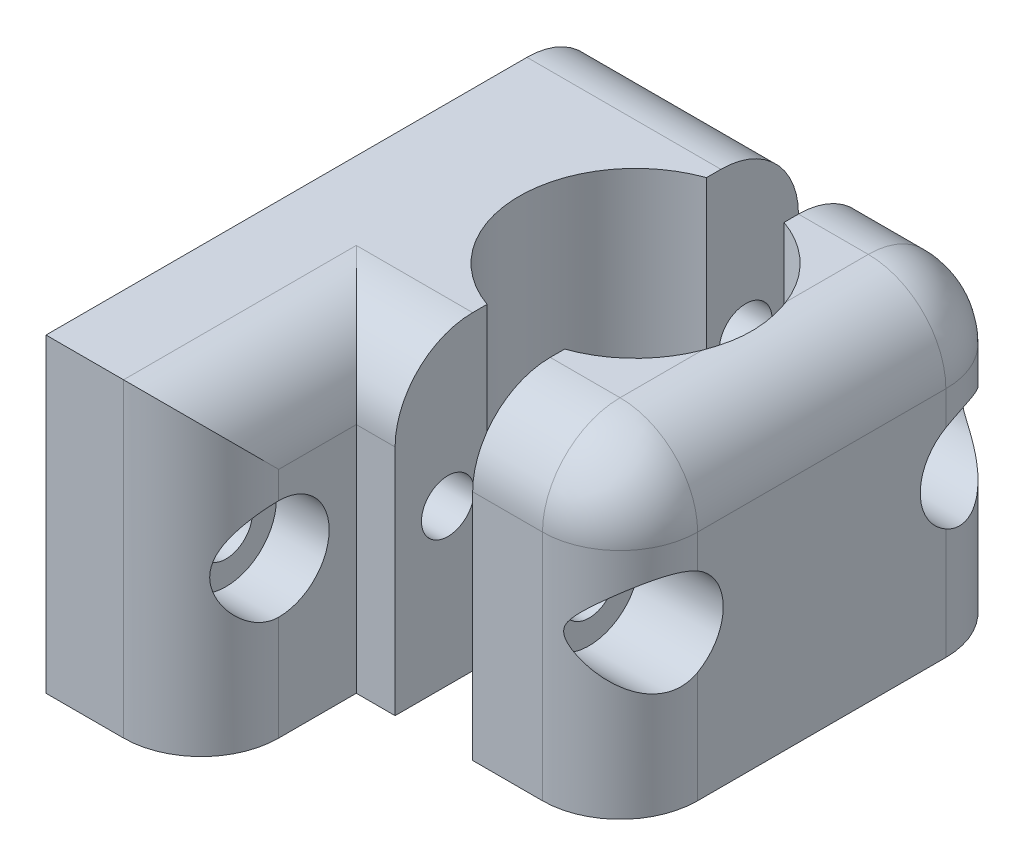
SolidWorks part; units mm, degrees
material "ABS"
ref_plane "Front Plane" through (0, 0, 0) normal (0, 0, 1) x (1, 0, 0)
ref_plane "Top Plane" through (0, 0, 0) normal (0, 1, 0) x (1, 0, 0)
ref_plane "Right Plane" through (0, 0, 0) normal (1, 0, 0) x (0, 0, -1)
sketch "Sketch1" plane through (0, 0, 0) normal (1, 0, 0) x (0, 0, -1)
  line L1 (-13, -10) -> (13, -10)
  line L2 (-13, -10) -> (-13, 10)
  line L3 (-13, 10) -> (13, 10)
  line L4 (13, -10) -> (13, 10)
  line L5 (-13, -10) -> (13, 10) construction
  line L6 (-13, 10) -> (13, -10) construction
  point P0 (0, 0)
  dimension "D1" = 20
  dimension "D2" = 26
extrude "Boss-Extrude1" add sketch "Sketch1" along normal blind 30
sketch "Sketch2" plane through (0, 10, 0) normal (0, 1, 0) x (1, 0, 0)
  line L0 (0, 13) -> (0, -13) construction
  circle A0 centre (15, 0) radius 7.5
  dimension "D1" = 15
  dimension "D2" = 15
extrude "Cut-Extrude1" cut sketch "Sketch2" against normal through all
ref_plane "Plane1" through (0, 0, 0) normal (0, 0, -1) x (-1, 0, 0)
sketch "Sketch4" plane through (0, 0, 13) normal (0, 0, 1) x (1, 0, 0)
  line L0 (30, -10) -> (0, -10) construction
  line L1 (0, 10) -> (10, 10)
  line L2 (0, 10) -> (0, -10)
  line L3 (0, -10) -> (10, -10)
  line L4 (10, 10) -> (10, -10)
  dimension "D1" = 10
extrude "Boss-Extrude2" add sketch "Sketch4" along normal blind 10
hole_wizard "CBORE for M3 Hex Socket Head Cap Screw1" positions "Sketch5" profile "Sketch6" counterbore size "M3" standard "ISO" end condition through all
sketch "Sketch5" plane through (10, 0, 0) normal (1, 0, 0) x (0, 0, -1)
  line L0 (-23, -10) -> (-23, 10) construction
  point P0 (-18, 0)
  dimension "D1" = 5
sketch "Sketch6" plane through (10, 0, 18) normal (0, 1, 0) x (0, 0, -1)
  line L0 (0, 0) -> (0, 10)
  line L1 (0, 10) -> (1.7, 10)
  line L3 (1.7, 10) -> (1.7, 3.4)
  line L4 (1.7, 3.4) -> (3.25, 3.4)
  line L5 (3.25, 3.4) -> (3.25, 0)
  line L7 (3.25, 0) -> (0, 0)
  line L11 (0, -6.35) -> (0, 107.95) construction
  dimension "Thru Hole Dia." = 3.4
  dimension "Thru Hole Depth" = 10
  dimension "C'Bore Dia." = 6.5
  dimension "C'Bore Depth" = 3.4
sketch "Sketch13" plane through (0, 10, 0) normal (0, 1, 0) x (1, 0, 0)
  line L0 (30, 13) -> (0, 13) construction
  line L1 (30, -13) -> (27, -13)
  line L2 (30, -13) -> (30, 13)
  line L3 (30, 13) -> (27, 13)
  line L4 (27, -13) -> (27, 13)
  dimension "D1" = 3
extrude "Cut-Extrude4" cut sketch "Sketch13" against normal through all
hole_wizard "CBORE for M3 Hex Socket Head Cap Screw3" positions "Sketch14" profile "Sketch15" counterbore size "M3" standard "ISO" end condition through all
sketch "Sketch14" plane through (27, 0, 0) normal (1, 0, 0) x (0, 0, -1)
  line L0 (-13, -10) -> (-13, 10) construction
  point P0 (-9.6, 0)
  dimension "D1" = 3.4
sketch "Sketch15" plane through (27, 0, 9.6) normal (0, 1, 0) x (0, 0, -1)
  line L0 (0, 0) -> (0, 27)
  line L1 (0, 27) -> (1.7, 27)
  line L3 (1.7, 27) -> (1.7, 5.4)
  line L4 (1.7, 5.4) -> (3.25, 5.4)
  line L5 (3.25, 5.4) -> (3.25, 0)
  line L7 (3.25, 0) -> (0, 0)
  line L11 (0, -6.35) -> (0, 107.95) construction
  dimension "Thru Hole Dia." = 3.4
  dimension "Thru Hole Depth" = 27
  dimension "C'Bore Dia." = 6.5
  dimension "C'Bore Depth" = 5.4
mirror "Mirror3" about plane through (0, 0, 0) normal (0, 0, -1) of "CBORE for M3 Hex Socket Head Cap Screw3"
sketch "Sketch12" plane through (0, 0, 0) normal (-1, 0, 0) x (0, 0, 1)
  line L7 (12.8332, 0) -> (11.2166, 2.8)
  line L8 (11.2166, 2.8) -> (7.9834, 2.8)
  line L9 (7.9834, 2.8) -> (6.3668, 0)
  line L10 (6.3668, 0) -> (7.9834, -2.8)
  line L11 (7.9834, -2.8) -> (11.2166, -2.8)
  line L12 (11.2166, -2.8) -> (12.8332, 0)
  circle A0 centre (9.6, 0) radius 2.8 construction
  dimension "D1" = 5.6
extrude "Cut-Extrude3" cut sketch "Sketch12" against normal blind 5
sketch "Sketch11" plane through (0, 10, 0) normal (0, 1, 0) x (1, 0, 0)
  line L0 (27, -13) -> (10, -13) construction
  line L1 (12.5, 13) -> (17.5, 13)
  line L2 (12.5, 13) -> (12.5, -13)
  line L3 (12.5, -13) -> (17.5, -13)
  line L4 (17.5, 13) -> (17.5, -13)
  line L5 (12.5, 13) -> (17.5, -13) construction
  line L6 (12.5, -13) -> (17.5, 13) construction
  point P0 (15, 0)
  dimension "D1" = 5
extrude "Cut-Extrude2" cut sketch "Sketch11" against normal through all
fillet "Fillet2" radius 5 4 edges at (10, 0, 23) (6.25, 10, -13) (10, 10, 18) (11.25, 10, 13)
fillet "Fillet3" radius 5 5 edges at (27, 0, 13) (27, 0, -13) (22.25, 10, -13) (22.25, 10, 13) (27, 10, 0)
